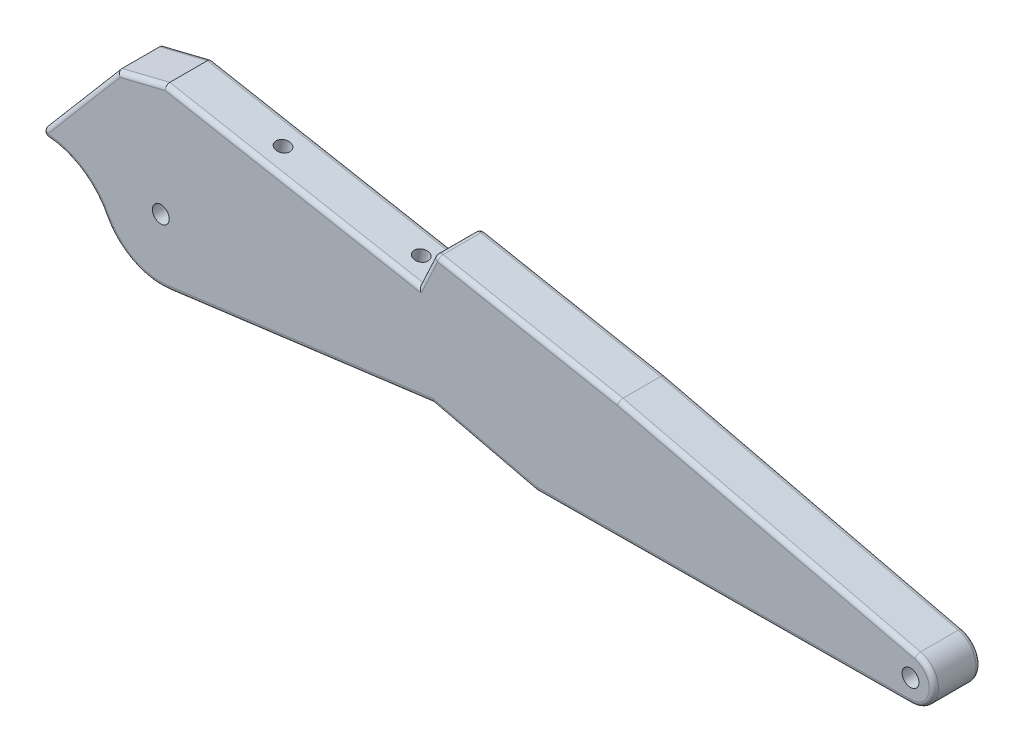
SolidWorks part; units mm, degrees
ref_plane "Front Plane" through (0, 0, 0) normal (0, 0, 1) x (1, 0, 0)
ref_plane "Top Plane" through (0, 0, 0) normal (0, 1, 0) x (1, 0, 0)
ref_plane "Right Plane" through (0, 0, 0) normal (1, 0, 0) x (0, 0, -1)
sketch "Sketch1" plane through (0, 0, 0) normal (0, 0, 1) x (1, 0, 0)
  line L1 (0.0486, -6.3498) -> (-101.5514, -7.1275)
  line L2 (-101.5514, -7.1275) -> (-129.54, -0.456)
  line L6 (-128.905, 34.925) -> (-133.35, 25.4)
  line L7 (-200.977, -9.7973) -> (-129.54, -0.456)
  line L8 (-133.35, 25.4) -> (-202.0358, 38.1)
  line L9 (-202.0358, 38.1) -> (-214.9475, 34.925)
  line L10 (-128.905, 34.925) -> (-79.1726, 25.4)
  line L11 (-79.1726, 25.4) -> (-128.905, 34.925) construction
  line L12 (-79.1726, 25.4) -> (1.4724, 6.1769)
  line L13 (-129.5991, 33.4375) -> (-133.35, 25.4) construction
  line L17 (-133.35, 25.4) -> (-202.0358, 38.1) construction
  line L18 (-17.145, -27.2472) -> (-129.54, -0.456) construction
  line L19 (-200.977, -9.7973) -> (-129.54, -0.456) construction
  line L20 (-107.0451, 30.7383) -> (-127.6185, 34.6786) construction
  line L21 (-177.7674, 44.0676) -> (-214.9475, 34.925) construction
  line L22 (-236.5375, 9.525) -> (-214.9475, 34.925)
  line L24 (-17.145, -27.2472) -> (-129.54, -0.456) construction
  line L25 (-234.7735, 11.6003) -> (-215.2133, 34.6123) construction
  line L29 (-79.1726, 25.4) -> (1.4724, 6.1769) construction
  line L31 (-129.54, -0.456) -> (-200.977, -9.7973) construction
  circle A0 centre (0, 0) radius 2.286
  arc A1 (0.0486, -6.3498) -> (1.4724, 6.1769) centre (0, 0) ccw
  circle A2 centre (-203.2, 7.203) radius 2.286
  arc A6 (-218.4137, -0.7023) -> (-200.977, -9.7973) centre (-203.2, 7.203) ccw
  circle A7 centre (-203.2, 7.203) radius 4.826 construction
  arc A8 (4.6019, -4.3755) -> (1.4724, 6.1769) centre (0, 0) ccw construction
  arc A9 (-236.5375, 9.525) -> (-218.4137, -0.7023) centre (-235.3179, -9.4859) cw
  arc A10 (-200.977, -9.7973) -> (-218.4137, -0.7023) centre (-203.2, 7.203) ccw construction
  arc A13 (-218.4137, -0.7023) -> (-233.9004, 9.5113) centre (-235.3179, -9.4859) ccw construction
  point P17 (105.4504, -19.602)
  point P18 (-71.2573, 0.0759)
  dimension "D1" = 4.572
  dimension "D2" = 101.6
extrude "Boss-Extrude1" add sketch "Sketch1" along normal blind 12.7
fillet "Fillet1" radius 1.27 26 edges at (-165.2585, -5.1266, 12.7) (-211.129, -7.9984, 12.7) (-38.8501, 15.7885, 12.7) (-225.9557, 7.1048, 0) (-211.129, -7.9984, 0) (-50.7514, -6.7387, 0) (-225.9557, 7.1048, 12.7) (-225.7425, 22.225, 12.7) (-208.4916, 36.5125, 12.7) (-167.6929, 31.75, 12.7) (-131.1275, 30.1625, 0) (-131.1275, 30.1625, 12.7) (-104.0388, 30.1625, 12.7) (-115.5457, -3.7917, 12.7) (-50.7514, -6.7387, 12.7) (-208.4916, 36.5125, 0) (-225.7425, 22.225, 0) (-167.6929, 31.75, 0) (-128.905, 34.925, 6.35) (-165.2585, -5.1266, 0) (-115.5457, -3.7917, 0) (-38.8501, 15.7885, 0) (-104.0388, 30.1625, 0) (6.3094, -0.7171, 12.7) (6.3094, -0.7171, 0) (-236.5375, 9.525, 6.35)
sketch "Sketch2" plane through (0, 0, 0) normal (0, 0, -1) x (-1, 0, 0)
  circle A0 centre (0, 0) radius 5.2387
  dimension "D1" = 10.4775
extrude "Cut-Extrude1" cut sketch "Sketch2" against normal blind 3.9688
sketch "Sketch3" plane through (0.1329, 0.719, 0) normal (0.1818, 0.9833, 0) x (0.9833, -0.1818, 0)
  circle A0 centre (-179.5561, -6.35) radius 1.905
  circle A1 centre (-141.4561, -6.35) radius 1.905
  dimension "D1" = 3.81
extrude "Cut-Extrude2" cut sketch "Sketch3" against normal blind 12.7
sketch "Sketch4" plane through (-142.0225, 120.7191, 0) normal (-0.7619, 0.6476, 0) x (0, 0, 1)
  line L0 (0, -143.212) -> (0, -113.0101) construction
  line L1 (1.27, -144.482) -> (11.43, -144.482) construction
  circle A0 centre (6.35, -138.132) radius 1.905
  dimension "D1" = 3.81
  dimension "D2" = 6.35
  dimension "D3" = 6.35
extrude "Cut-Extrude3" cut sketch "Sketch4" against normal blind 12.7
